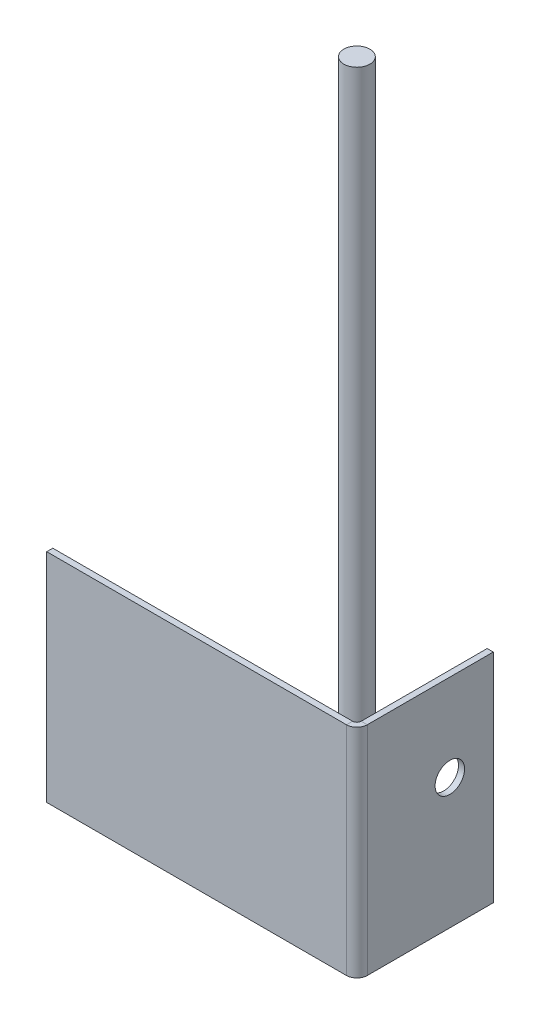
SolidWorks part; units mm, degrees
note: The reader was unsure of these and kept them because the rebuilt part matched: flange length of "Edge-Flange1".
ref_plane "Front Plane" through (0, 0, 0) normal (0, 0, 1) x (1, 0, 0)
ref_plane "Top Plane" through (0, 0, 0) normal (0, 1, 0) x (1, 0, 0)
ref_plane "Right Plane" through (0, 0, 0) normal (1, 0, 0) x (0, 0, -1)
sketch "Sketch1" plane through (0, 0, 0) normal (0, 0, 1) x (1, 0, 0)
  line L1 (-17.5, 12.5) -> (17.5, 12.5)
  line L2 (-17.5, 12.5) -> (-17.5, -12.5)
  line L3 (-17.5, -12.5) -> (17.5, -12.5)
  line L4 (17.5, 12.5) -> (17.5, -12.5)
  line L5 (-17.5, 12.5) -> (17.5, -12.5) construction
  line L6 (-17.5, -12.5) -> (17.5, 12.5) construction
  point P0 (0, 0)
  dimension "D1" = 35
  dimension "D2" = 25
base flange "Base-Flange1" sketch "Sketch1" thickness 0.7 reverse thickness direction no parameters "D1"=0.5
sketch "Sketch6" plane through (0, -12.5, 0) normal (0, 1, 0) x (1, 0, 0)
  line L2 (-17.5, 0.7) -> (17.5, 0.7) construction
  circle A0 centre (16, 2.2) radius 1.5
  dimension "D1" = 3
  dimension "D2" = 1.5
extrude "Boss-Extrude1" add sketch "Sketch6" along normal blind 90 separate body
edge flange "Edge-Flange1" sketch "Sketch9" flange angle 90 flange length 15 flange position material outside bend radius 0.5 thickness 0.7 relief rectangular parameters "D6"=10
sketch "Sketch9" plane through (17.5, 0, -0.7) normal (1, 0, 0) x (0, -1, 0)
  line L2 (-12.5, 0) -> (-12.5, 15)
  line L3 (-12.5, 15) -> (12.5, 15)
  line L4 (12.5, 15) -> (12.5, 0)
  line L7 (12.5, 0) -> (-12.5, 0) construction
  line L8 (12.5, 0) -> (-12.5, 0)
bend "EdgeBend1" bend radius 0.5 bend angle 90 parameters "D5"=1
sketch "Sketch10" plane through (17.5, 0, 0) normal (-1, 0, 0) x (0, 0, 1)
  line L0 (-10.7, 12.6538) -> (-10.7, -12.5) construction
  line L1 (-1.2, -12.5) -> (-15.7, -12.5) construction
  line L2 (-0.7, 12.5) -> (-0.7, -12.5) construction
  circle A0 centre (-10.7, 2.5) radius 1.696
  dimension "D1" = 10
  dimension "D2" = 15
extrude "Cut-Extrude1" cut sketch "Sketch10" against normal up to surface (0.7 mm away) up to face at (18.2, 0, -8.45)
sketch "Bend-Lines1" [suppressed] plane through (0, 0, 0) normal (0, 1, 0) x (1, 0, 0)
sketch "Bounding-Box1" [suppressed] plane through (0, 0, 0) normal (0, 1, 0) x (1, 0, 0)
sheet metal parameters "Sheet-Metal1" thickness 0.7 parameters "D1"=0.5
flat pattern "Flat-Pattern1" [suppressed]
sketch "Bend-Lines2" plane through (0, 0, 0) normal (0, 1, 0) x (1, 0, 0)
sketch3d "Bounding-Box2" [suppressed]
  line L0 (15, -12.5, 0) -> (-15, -12.5, 0) construction
  line L1 (15, 12.5, 0) -> (-15, 12.5, 0) construction
  line L2 (15, -12.5, 0) -> (15, 12.5, 0) construction
  line L3 (-15, -12.5, 0) -> (-15, 12.5, 0) construction
sheet metal parameters "Sheet-Metal3" thickness 0.7 parameters "D1"=0.5
flat pattern "Flat-Pattern1" [suppressed]
sketch "Bend-Lines2" plane through (0, 0, 0) normal (0, 0, 1) x (1, 0, 0)
  line L0 (15.1676, -12.5) -> (15.1676, 12.5) construction
  line L1 (15.1676, -12.5) -> (15.1676, 12.5) construction
sketch3d "Bounding-Box2" [suppressed]
  line L0 (-15, -12.5, 0) -> (30.3352, -12.5, 0) construction
  line L1 (-15, 12.5, 0) -> (30.3352, 12.5, 0) construction
  line L2 (-15, -12.5, 0) -> (-15, 12.5, 0) construction
  line L3 (30.3352, -12.5, 0) -> (30.3352, 12.5, 0) construction
bend of the flat pattern "Flatten-<EdgeBend1>1"
sketch "Sketch10-1" [suppressed] plane through (14.6352, 0, -0.7) normal (0, 0, -1) x (-1, 0, 0)
  line L0 (-10.7, 12.6538) -> (-10.7, -12.5) construction
  line L2 (29.6352, 12.5) -> (29.6352, -12.5) construction
  circle A0 centre (-10.7, 2.5) radius 1.696
  dimension "D1" = 40.3352
  dimension "D2" = 15
sheet metal parameters "Sheet-Metal4" thickness 0.7 parameters "D1"=0.5
flat pattern "Flat-Pattern1" [suppressed]
sketch "Bend-Lines2" plane through (0, 0, 0) normal (0, 0, 1) x (1, 0, 0)
  line L0 (17.6676, -12.5) -> (17.6676, 12.5) construction
  line L1 (17.6676, -12.5) -> (17.6676, 12.5) construction
sketch3d "Bounding-Box2" [suppressed]
  line L0 (-17.5, -12.5, 0) -> (32.8352, -12.5, 0) construction
  line L1 (-17.5, 12.5, 0) -> (32.8352, 12.5, 0) construction
  line L2 (-17.5, -12.5, 0) -> (-17.5, 12.5, 0) construction
  line L3 (32.8352, -12.5, 0) -> (32.8352, 12.5, 0) construction
bend of the flat pattern "Flatten-<EdgeBend1>1"
sketch "Sketch10-1" plane through (17.1352, 0, -0.7) normal (0, 0, -1) x (-1, 0, 0)
  line L0 (-10.7, 12.6538) -> (-10.7, -12.5) construction
  line L2 (34.6352, 12.5) -> (34.6352, -12.5) construction
  circle A0 centre (-10.7, 2.5) radius 1.696
  dimension "D1" = 45.3352
  dimension "D2" = 15
